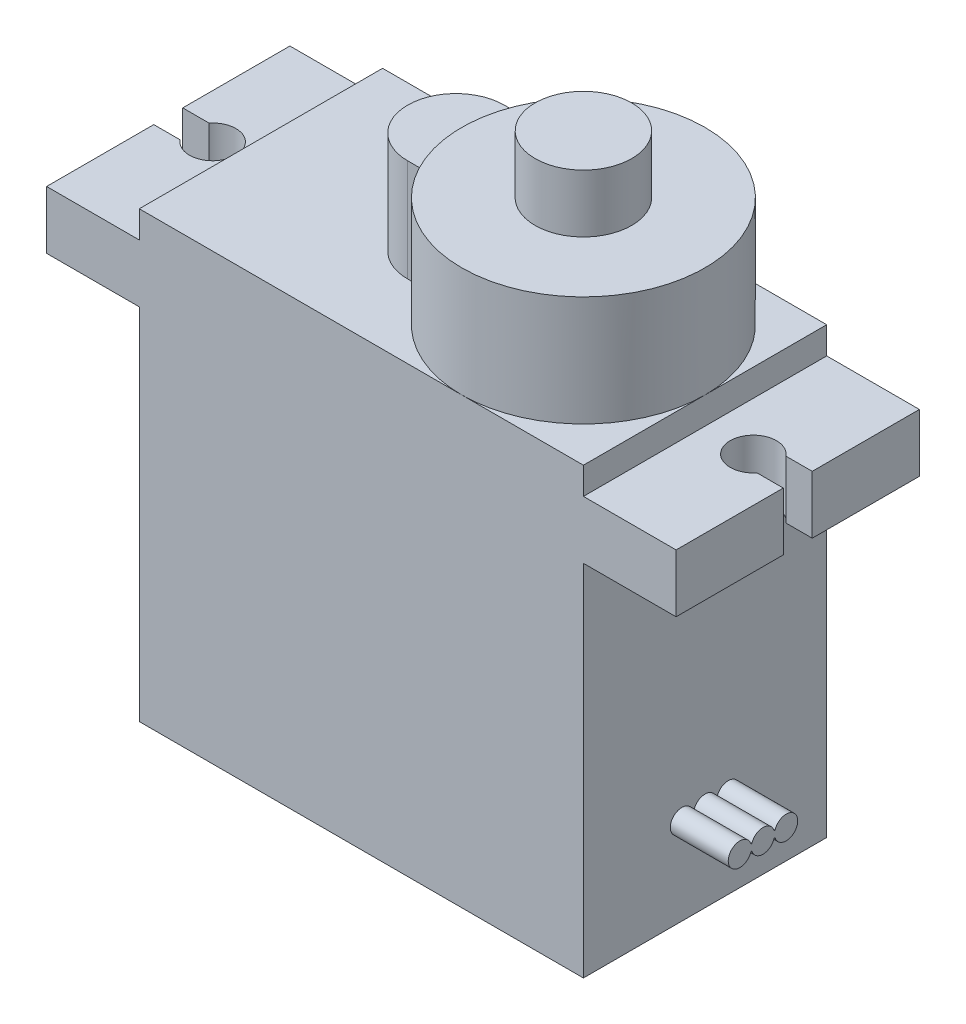
SolidWorks part; units mm, degrees
other "Main Body"
other "Cables"
material "ABS"
ref_plane "Front Plane" through (0, 0, 0) normal (0, 0, 1) x (1, 0, 0)
ref_plane "Top Plane" through (0, 0, 0) normal (0, 1, 0) x (1, 0, 0)
ref_plane "Right Plane" through (0, 0, 0) normal (1, 0, 0) x (0, 0, -1)
sketch "Sketch1" plane through (0, 0, 0) normal (0, 1, 0) x (1, 0, 0)
  line L1 (0, 0) -> (23, 0)
  line L2 (0, 0) -> (0, 12.6)
  line L3 (0, 12.6) -> (23, 12.6)
  line L4 (23, 0) -> (23, 12.6)
  dimension "D1" = 12.6
  dimension "D2" = 23
extrude "Boss-Extrude1" add sketch "Sketch1" along normal blind 23
sketch "Sketch2" plane through (0, 0, 0) normal (0, 0, 1) x (1, 0, 0)
  line L0 (0, 23) -> (0, 0) construction
  line L1 (0, 21.6) -> (-4.8, 21.6)
  line L2 (0, 21.6) -> (0, 18.6)
  line L3 (0, 18.6) -> (-4.8, 18.6)
  line L4 (-4.8, 21.6) -> (-4.8, 18.6)
  line L5 (11.5, 23) -> (11.5, 18.2161) construction
  line L6 (0, 23) -> (23, 23) construction
  line L7 (27.8, 21.6) -> (27.8, 18.6)
  line L8 (23, 18.6) -> (27.8, 18.6)
  line L9 (23, 21.6) -> (23, 18.6)
  line L10 (23, 21.6) -> (27.8, 21.6)
  dimension "D1" = 4.8
  dimension "D2" = 3
  dimension "D3" = 1.4
extrude "Boss-Extrude2" add sketch "Sketch2" against normal up to surface (12.6 mm away) up to face at (11.5, 11.5, -12.6)
sketch "Sketch3" plane through (0, 23, 0) normal (0, 1, 0) x (1, 0, 0)
  line L0 (23, 12.6) -> (0, 12.6) construction
  line L1 (23, 12.6) -> (23, 0) construction
  line L2 (0, 0) -> (23, 0) construction
  circle A0 centre (16.7, 6.3) radius 6.3
extrude "Boss-Extrude3" add sketch "Sketch3" along normal blind 5.7
sketch "Sketch4" plane through (0, 23, 0) normal (0, 1, 0) x (1, 0, 0)
  line L0 (10.1, 3.8) -> (10.9173, 3.8)
  line L1 (10.1, 8.8) -> (10.9173, 8.8)
  line L2 (0, 6.3) -> (10.4, 6.3) construction
  line L4 (0, 12.6) -> (0, 0) construction
  line L5 (7.6, 8.3717) -> (7.6, 3.8) construction
  line L6 (10.4, 7.8008) -> (10.4, 4.9905) construction
  arc A0 (16.7, 12.6) -> (16.7, 0) centre (16.7, 6.3) ccw construction
  circle A1 centre (16.7, 6.3) radius 6.3 construction
  arc A2 (10.1, 8.8) -> (10.1, 3.8) centre (10.1, 6.3) ccw
  arc A3 (10.9173, 8.8) -> (10.9173, 3.8) centre (16.7, 6.3) ccw
  dimension "D1" = 5
  dimension "D2" = 2.8
extrude "Boss-Extrude4" add sketch "Sketch4" along normal blind 5.3
sketch "Sketch5" plane through (0, 21.6, 0) normal (0, 1, 0) x (1, 0, 0)
  line L0 (-4.8, 7.05) -> (-3.4367, 7.05)
  line L1 (-4.8, 12.6) -> (-4.8, 0) construction
  line L2 (-4.8, 5.55) -> (-3.4367, 5.55)
  line L3 (-2.5, 6.3) -> (-4.8, 6.3) construction
  line L4 (-1.3, 7.8261) -> (-1.3, 4.3925) construction
  line L5 (-4.8, 7.05) -> (-4.8, 5.55)
  line L6 (0, 13.4957) -> (23, 13.4957) construction
  line L7 (11.5, 13.4957) -> (11.5, 0) construction
  line L8 (0, 0) -> (16.7, 0) construction
  line L9 (25.5, 6.3) -> (27.8, 6.3) construction
  line L10 (27.8, 7.05) -> (27.8, 5.55)
  line L11 (27.8, 5.55) -> (26.4367, 5.55)
  line L12 (27.8, 7.05) -> (26.4367, 7.05)
  arc A0 (-3.4367, 5.55) -> (-3.4367, 7.05) centre (-2.5, 6.3) ccw
  arc A1 (26.4367, 5.55) -> (26.4367, 7.05) centre (25.5, 6.3) cw
  dimension "D1" = 2.4
  dimension "D2" = 1.5
  dimension "D3" = 3.5
extrude "Cut-Extrude1" cut sketch "Sketch5" against normal up to surface (3 mm away) contours A0 L0 L5 L2 | A1 L12 L10 L11 up to face at (-2.4, 18.6, -7.875)
sketch "Sketch6" plane through (0, 28.7, 0) normal (0, 1, 0) x (1, 0, 0)
  circle A0 centre (16.7, 6.3) radius 2.5
  circle A1 centre (16.7, 6.3) radius 6.3 construction
  dimension "D1" = 5
sketch "Sketch9"
sketch "Sketch10"
sketch "Sketch11" plane through (23, 0, 0) normal (1, 0, 0) x (0, 0, -1)
  line L0 (6.3, 4.5) -> (6.3, 0) construction
  line L1 (0, 0) -> (12.6, 0) construction
  line L2 (5.1, 5.1) -> (7.5, 5.1) construction
  line L3 (5.675, 4.6714) -> (5.725, 4.6714)
  line L4 (6.875, 4.6714) -> (6.925, 4.6714)
  line L5 (5.675, 4.3286) -> (5.725, 4.3286)
  line L6 (6.875, 4.3286) -> (6.925, 4.3286)
  line L7 (5.1, 5.1) -> (5.1, 3.9) construction
  line L8 (6.3, 5.1) -> (6.3, 3.9) construction
  line L9 (7.5, 5.1) -> (7.5, 3.9) construction
  arc A0 (5.725, 4.3286) -> (6.875, 4.3286) centre (6.3, 4.5) ccw
  arc A1 (5.675, 4.6714) -> (5.675, 4.3286) centre (5.1, 4.5) ccw
  arc A2 (6.925, 4.3286) -> (6.925, 4.6714) centre (7.5, 4.5) ccw
  arc A3 (6.875, 4.6714) -> (5.725, 4.6714) centre (6.3, 4.5) ccw
  dimension "D1" = 1.2
  dimension "D2" = 5.1
  dimension "D3" = 0.05
extrude "Boss-Extrude6" add sketch "Sketch11" along normal blind 3 separate body contours A3 L3 A1 L5 A0 L6 A2 L4
extrude "Boss-Extrude7" add sketch "Sketch6" along normal blind 3 contours A0
ref_axis "Axis1" through (16.7, 31.7, -6.3) along (0, -1, 0)
ref_plane "Plane1" through (16.7, 0, 0) normal (1, 0, 0) x (0, 0, -1)
ref_plane "Plane2" through (0, 0, -6.3) normal (0, 0, 1) x (1, 0, 0)
